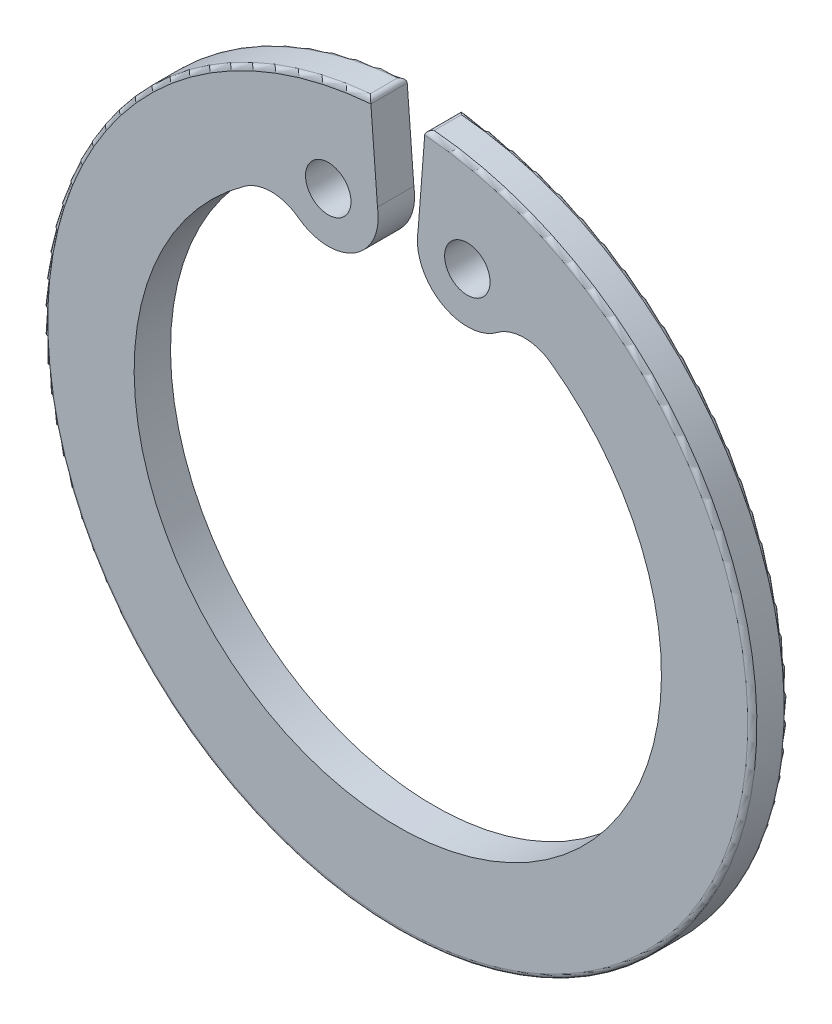
SolidWorks part; units mm, degrees
ref_plane "Front Plane" through (0, 0, 0) normal (0, 0, 1) x (1, 0, 0)
ref_plane "Top Plane" through (0, 0, 0) normal (0, 1, 0) x (1, 0, 0)
ref_plane "Right Plane" through (0, 0, 0) normal (1, 0, 0) x (0, 0, -1)
sketch "Sketch1" plane through (0, 0, 0) normal (0, 0, 1) x (1, 0, 0)
  line L2 (1.5, 19.4422) -> (0, 0)
  line L3 (0, 0) -> (-1.5, 19.4422)
  line L4 (-0.75, 9.7211) -> (0.75, 9.7211) construction
  circle A0 centre (0, 0) radius 19.5
  circle A1 centre (0, 0) radius 14.5
  dimension "D1" = 39
  dimension "D2" = 5
  dimension "D3" = 3
extrude "Boss-Extrude1" add sketch "Sketch1" along normal blind 1 and the other way blind 1 contours A1 L3 A0 L2 region at (13.9047, 12.8732, 0)
sketch "Sketch2" plane through (0, 0, 0) normal (0, 0, 1) x (1, 0, 0)
  circle A3 centre (-3.8248, 13.9864) radius 2.75
  circle A5 centre (-3.8248, 13.9864) radius 1.25
  circle A6 centre (3.8248, 13.9864) radius 2.75
  circle A7 centre (3.8248, 13.9864) radius 1.25
  arc A8 (-1.1154, 14.457) -> (1.1154, 14.457) centre (0, 0) ccw construction
  point P2 (3.9777, 13.9437)
  point P11 (-4.0392, 13.926)
  point P16 (4.4307, 13.8065)
  dimension "D1" = 2.5
  dimension "D2" = 1.5
extrude "Boss-Extrude2" add sketch "Sketch2" along normal up to surface (1 mm away) and the other way up to surface (1 mm away) up to face at (0, -0.0252, 1) other way up to face at (0, -0.0252, -1)
fillet "Fillet1" radius 2.5 2 edges at (6.3967, 13.0128, 0) (-6.3967, 13.0128, 0)
extrude "Cut-Extrude1" cut sketch "Sketch2<2>" against normal through all both and the other way through all contours A5 | A7 region at (-3.8248, 13.9864, 0) region at (3.8248, 13.9864, 0)
sketch "Sketch2<2>" plane through (0, 0, 0) normal (0, 0, 1) x (1, 0, 0) same geometry as "Sketch2"
fillet "Fillet4" radius 0.25 4 edges at (0, -19.5, -1) (-1.5, 19.4422, 0) (0, -19.5, 1) (1.5, 19.4422, 0)
